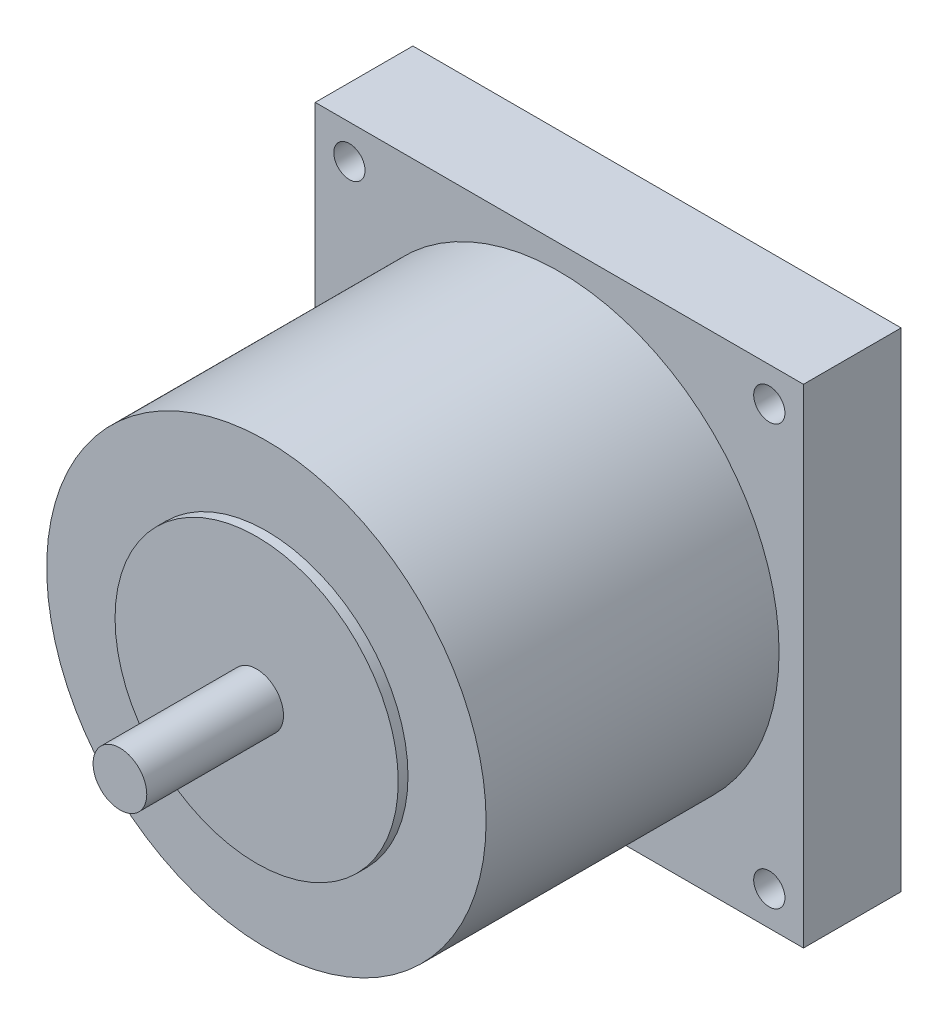
SolidWorks part; units mm, degrees
ref_plane "Front Plane" through (0, 0, 0) normal (0, 0, 1) x (1, 0, 0)
ref_plane "Top Plane" through (0, 0, 0) normal (0, 1, 0) x (1, 0, 0)
ref_plane "Right Plane" through (0, 0, 0) normal (1, 0, 0) x (0, 0, -1)
sketch "Sketch2" plane through (0, 0, 0) normal (0, 0, 1) x (1, 0, 0)
  line L1 (-25, -25) -> (25, -25)
  line L2 (-25, -25) -> (-25, 25)
  line L3 (-25, 25) -> (25, 25)
  line L4 (25, -25) -> (25, 25)
  line L5 (-25, -25) -> (25, 25) construction
  line L6 (-25, 25) -> (25, -25) construction
  circle A0 centre (0, 0) radius 22.5
  circle A1 centre (0, 0) radius 14.5
  circle A2 centre (0, 0) radius 2.75
  point P0 (0, 0)
  dimension "D3" = 45
  dimension "D4" = 8
  dimension "D5" = 5.5
  dimension "D1" = 50
  dimension "D2" = 50
extrude "Boss-Extrude1" add sketch "Sketch2" along normal blind 10 contours L1 L4 L3 L2 A0 | A2 | A1 A2 | A0 A1 region at (-24.2929, 0, 0) region at (-21.8636, 0, 0) region at (-14.0899, 0, 0) region at (0, 0, 0)
extrude "Boss-Extrude2" add sketch "Sketch2<3>" along normal blind 40 contours A0 A1 | A1 A2 | A2 region at (-21.8636, 0, 0) region at (-14.0899, 0, 0) region at (0, 0, 0)
sketch "Sketch2<3>" plane through (0, 0, 0) normal (0, 0, 1) x (1, 0, 0) same geometry as "Sketch2"
extrude "Boss-Extrude3" add sketch "Sketch2<4>" along normal blind 41 contours A1 A2 region at (-14.0899, 0, 0)
sketch "Sketch2<4>" plane through (0, 0, 0) normal (0, 0, 1) x (1, 0, 0) same geometry as "Sketch2"
extrude "Boss-Extrude4" add sketch "Sketch2<5>" along normal blind 55 contours A2 region at (0, 0, 0)
sketch "Sketch2<5>" plane through (0, 0, 0) normal (0, 0, 1) x (1, 0, 0) same geometry as "Sketch2"
sketch "Sketch4" plane through (0, 0, 0) normal (0, 0, -1) x (-1, 0, 0)
  line L0 (-25, 21.5) -> (25, 21.5) construction
  line L1 (-25, -25) -> (-25, 25) construction
  line L2 (25, -25) -> (25, 25) construction
  line L3 (-21.5, 25) -> (-21.5, -25) construction
  line L4 (25, 25) -> (-25, 25) construction
  line L5 (25, -25) -> (-25, -25) construction
  line L6 (0, 25) -> (0, -25) construction
  line L7 (-25, 0) -> (25, 0) construction
  circle A0 centre (-21.5, 21.5) radius 1.6
  circle A1 centre (-21.5, -21.5) radius 1.6
  circle A2 centre (21.5, -21.5) radius 1.6
  circle A3 centre (21.5, 21.5) radius 1.6
  point P18 (0, 0)
  dimension "D1" = 3.2
  dimension "D2" = 3.5
  dimension "D3" = 3.5
extrude "Cut-Extrude1" cut sketch "Sketch4" against normal through all
